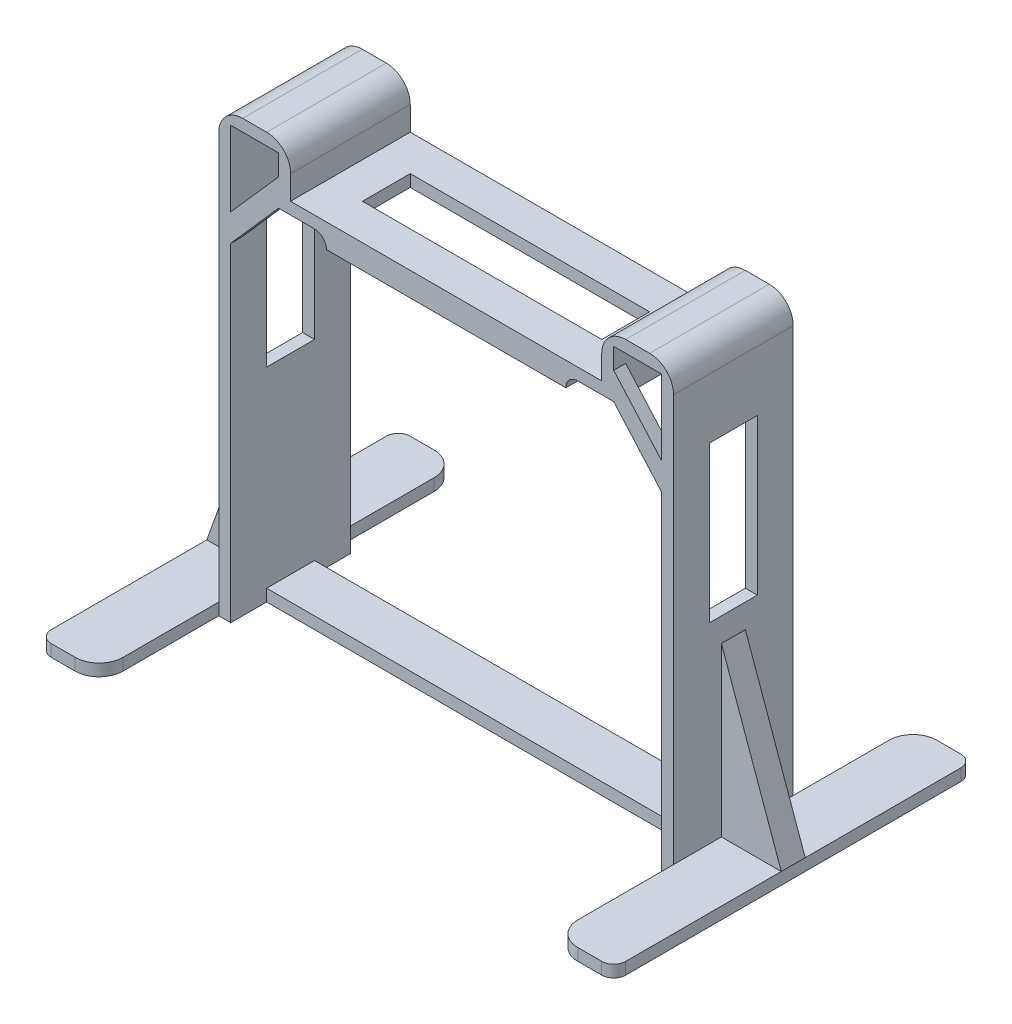
SolidWorks part; units mm, degrees
material "PEI"
ref_plane "前视基准面" through (0, 0, 0) normal (0, 0, 1) x (1, 0, 0)
ref_plane "上视基准面" through (0, 0, 0) normal (0, 1, 0) x (1, 0, 0)
ref_plane "右视基准面" through (0, 0, 0) normal (1, 0, 0) x (0, 0, -1)
other "Configuration Table"
sketch "草图1" plane through (0, 0, 0) normal (0, 0, 1) x (1, 0, 0)
  line L0 (0, 0) -> (30, 0)
  line L1 (30, 0) -> (30, 180)
  line L2 (30, 180) -> (50, 180)
  line L3 (50, 180) -> (50, 160)
  line L4 (50, 160) -> (190, 160)
  line L5 (190, 160) -> (190, 180)
  line L6 (190, 180) -> (210, 180)
  line L7 (210, 180) -> (210, 0)
  line L8 (210, 0) -> (240, 0)
  line L9 (240, 0) -> (240, 5)
  line L10 (240, 5) -> (215, 5)
  line L11 (215, 5) -> (215, 185)
  line L12 (215, 185) -> (185, 185)
  line L13 (185, 185) -> (185, 165)
  line L14 (185, 165) -> (55, 165)
  line L15 (55, 165) -> (55, 185)
  line L16 (55, 185) -> (25, 185)
  line L17 (25, 185) -> (25, 5)
  line L18 (25, 5) -> (0, 5)
  line L19 (0, 5) -> (0, 0)
  point P23 (40.0681, 6.8454)
  dimension "D1" = 5
  dimension "D2" = 5
  dimension "D3" = 5
  dimension "D4" = 5
  dimension "D5" = 30
  dimension "D6" = 30
  dimension "D7" = 130
  dimension "D8" = 5
  dimension "D9" = 180
  dimension "D10" = 20
extrude "凸台-拉伸1" add sketch "草图1" along normal blind 50
sketch "草图2" plane through (0, 0, 0) normal (-1, 0, 0) x (0, 0, 1)
  line L0 (50, 5) -> (0, 5) construction
  line L1 (15, 5) -> (35.0007, 5)
  line L2 (15, 5) -> (15, 0)
  line L3 (15, 0) -> (35.0007, 0)
  line L4 (35.0007, 5) -> (35.0007, 0)
  line L5 (50, 0) -> (0, 0) construction
  line L6 (0, 5) -> (0, 0) construction
  dimension "D1" = 20.0007
  dimension "D2" = 15
extrude "凸台-拉伸2" add sketch "草图2" against normal up to surface (240 mm away) up to face at (240, 2.5, 25)
sketch "草图3" plane through (0, 0, 0) normal (0, 0, -1) x (-1, 0, 0)
  line L1 (-240, 0) -> (-215, 0)
  line L2 (-240, 0) -> (-240, 5)
  line L3 (-240, 5) -> (-215, 5)
  line L4 (-215, 0) -> (-215, 5)
  line L5 (0, 0) -> (-25, 0)
  line L6 (0, 0) -> (0, 5)
  line L7 (0, 5) -> (-25, 5)
  line L8 (-25, 0) -> (-25, 5)
extrude "凸台-拉伸3" add sketch "草图3" along normal blind 50 and the other way blind 100
ref_plane "基准面1" through (0, 0, 25) normal (0, 0, -1) x (-1, 0, 0)
sketch "草图4" plane through (0, 0, 25) normal (0, 0, -1) x (-1, 0, 0)
  line L0 (-240, 5) -> (-215, 75)
  line L1 (-215, 5) -> (-215, 185) construction
  dimension "D1" = 70
rib "筋2" sketch "草图4" sketch "草图4" thickness 10 extrusion direction parallel to sketch draft on no parameters "D1"=10
sketch "草图5" plane through (0, 0, 25) normal (0, 0, -1) x (-1, 0, 0)
  line L0 (-25, 75) -> (0, 5)
  line L1 (-25, 185) -> (-25, 5) construction
  dimension "D1" = 70
rib "筋3" sketch "草图5" sketch "草图5" thickness 10 extrusion direction parallel to sketch draft on no parameters "D1"=10
sketch "草图6" plane through (215, 0, 0) normal (1, 0, 0) x (0, 0, -1)
  line L0 (-50, 5) -> (-50, 185) construction
  line L1 (-35, 150) -> (-15, 150)
  line L2 (-35, 150) -> (-35, 85)
  line L3 (-35, 85) -> (-15, 85)
  line L4 (-15, 150) -> (-15, 85)
  line L5 (-30, 75) -> (-20, 75) construction
  line L6 (-50, 160) -> (0, 160) construction
  dimension "D1" = 15
  dimension "D2" = 20
  dimension "D3" = 10
  dimension "D4" = 10
extrude "切除-拉伸1" cut sketch "草图6" against normal up to surface (190 mm away) up to face at (25, 67.5, 25)
sketch "草图7" plane through (0, 165, 0) normal (0, 1, 0) x (1, 0, 0)
  line L0 (55, -50) -> (55, 0) construction
  line L1 (70, -15) -> (170, -15)
  line L2 (70, -15) -> (70, -35)
  line L3 (70, -35) -> (170, -35)
  line L4 (170, -15) -> (170, -35)
  line L5 (185, -50) -> (185, 0) construction
  line L6 (185, 0) -> (55, 0) construction
  line L7 (185, -50) -> (55, -50) construction
  dimension "D1" = 15
  dimension "D2" = 15
  dimension "D3" = 15
  dimension "D4" = 15
extrude "切除-拉伸2" cut sketch "草图7" against normal up to surface (5 mm away) up to face at (120, 160, 25)
sketch "草图9" plane through (0, 0, 0) normal (0, 0, -1) x (-1, 0, 0)
  line L0 (-190, 160) -> (-210, 137.3005)
  line L1 (-210, 180) -> (-210, 0) construction
  line L2 (-210, 137.3005) -> (-210, 148.6455)
  line L3 (-210, 148.6455) -> (-190, 171.345)
  line L4 (-190, 171.345) -> (-190, 160)
  dimension "D1" = 7.5
extrude "凸台-拉伸5" add sketch "草图9" against normal blind 5
mirror "镜向1" about plane through (0, 0, 25) normal (0, 0, -1) of "凸台-拉伸5"
ref_plane "基准面2" through (120, 0, 0) normal (1, 0, 0) x (0, 0, -1)
mirror "镜向2" about plane through (120, 0, 0) normal (1, 0, 0) of "镜向1"
sketch "草图10" plane through (120, 0, 0) normal (1, 0, 0) x (0, 0, -1)
  line L0 (-5, 160) -> (0, 160) construction
  line L1 (-50, 160) -> (-45, 160) construction
  line L2 (-45, 160) -> (-5, 160) construction
  line L3 (-5, 160) -> (0, 160)
  line L4 (-50, 160) -> (-45, 160)
  line L5 (-45, 160) -> (-5, 160)
  line L7 (-50, 160) -> (-45, 160)
  line L8 (-50, 160) -> (-50, 155)
  line L9 (-50, 155) -> (-45, 155)
  line L10 (-45, 160) -> (-45, 155)
  dimension "D1" = 5
  dimension "D2" = 5
extrude "凸台-拉伸6" add sketch "草图10" along normal up to surface and the other way up to surface contours L10 L4 L8 L9 region at (120, 157.5, 47.5) up to face at (170, 162.5, 25) other way up to face at (70, 162.5, 25)
mirror "镜向3" about plane through (0, 0, 25) normal (0, 0, -1) of "凸台-拉伸6"
fillet "圆角1" radius 5 1 edges at (70, 160, 47.5) type face fillet first side face at (70, 157.5, 47.5) second side face at (120, 160, 25)
fillet "圆角2" radius 5 1 edges at (170, 160, 47.5) type face fillet first side face at (170, 157.5, 47.5) second side face at (120, 160, 25)
fillet "圆角3" radius 5 1 edges at (170, 160, 2.5) type face fillet first side face at (170, 157.5, 2.5) second side face at (120, 160, 25)
fillet "圆角4" radius 5 1 edges at (70, 160, 2.5) type face fillet first side face at (70, 157.5, 2.5) second side face at (120, 160, 25)
fillet "圆角5" radius 10 8 edges at (215, 2.5, 100) (25, 2.5, 100) (25, 2.5, -50) (215, 2.5, -50) (185, 185, 25) (215, 185, 25) (25, 185, 25) (55, 185, 25)
fillet "圆角6" radius 5 4 edges at (0, 2.5, 100) (0, 2.5, -50) (240, 2.5, 100) (240, 2.5, -50)
